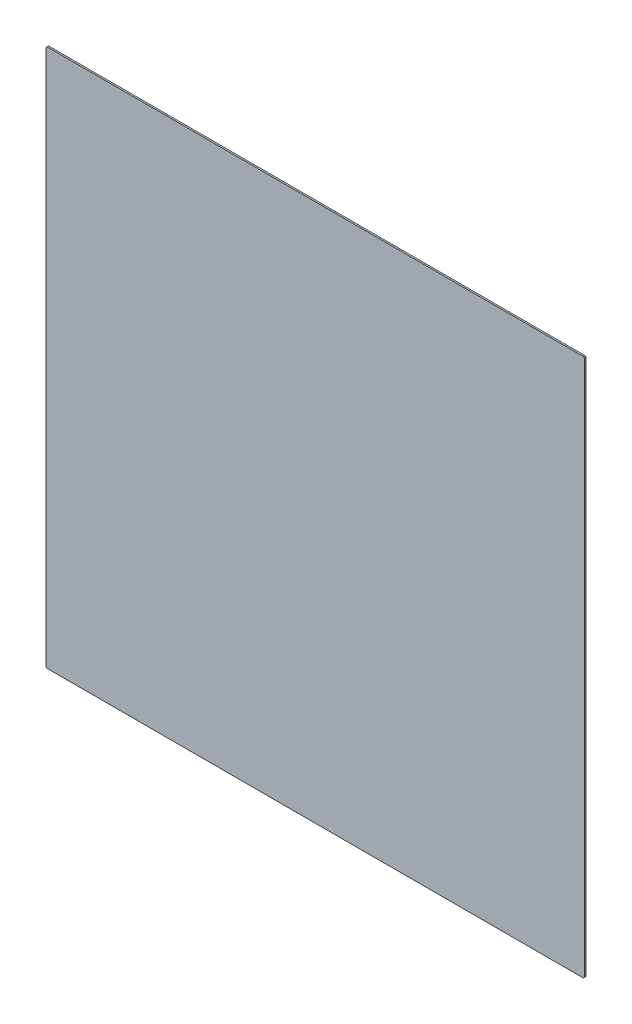
SolidWorks part; units mm, degrees
ref_plane "前视基准面" through (0, 0, 0) normal (0, 0, 1) x (1, 0, 0)
ref_plane "上视基准面" through (0, 0, 0) normal (0, 1, 0) x (1, 0, 0)
ref_plane "右视基准面" through (0, 0, 0) normal (1, 0, 0) x (0, 0, -1)
other "Configuration Table"
sketch "草图1" plane through (0, 0, 0) normal (0, 0, 1) x (1, 0, 0)
  line L1 (-520, 520) -> (520, 520)
  line L2 (-520, 520) -> (-520, -520)
  line L3 (-520, -520) -> (520, -520)
  line L4 (520, 520) -> (520, -520)
  line L5 (-520, 520) -> (520, -520) construction
  line L6 (-520, -520) -> (520, 520) construction
  point P0 (0, 0)
  dimension "D1" = 1040
  dimension "D2" = 1040
base flange "基体-法兰1" sketch "草图1" thickness 3 reverse thickness direction no parameters "D1"=2.5
chamfer "倒角1" distance 2 angle 45 4 edges at (520, 520, -1.5) (-520, 520, -1.5) (-520, -520, -1.5) (520, -520, -1.5)
sketch "折弯-线1" plane through (0, 0, 0) normal (0, 1, 0) x (1, 0, 0)
sketch "边界框1" plane through (0, 0, 0) normal (0, 1, 0) x (1, 0, 0)
sheet metal parameters "钣金6" thickness 3 parameters "D1"=2.5
flat pattern "平板型式6" [suppressed]
sketch "折弯-线2" plane through (0, 0, 0) normal (0, 1, 0) x (1, 0, 0)
sketch "边界框2" [suppressed] plane through (0, 0, 0) normal (0, 1, 0) x (1, 0, 0)
